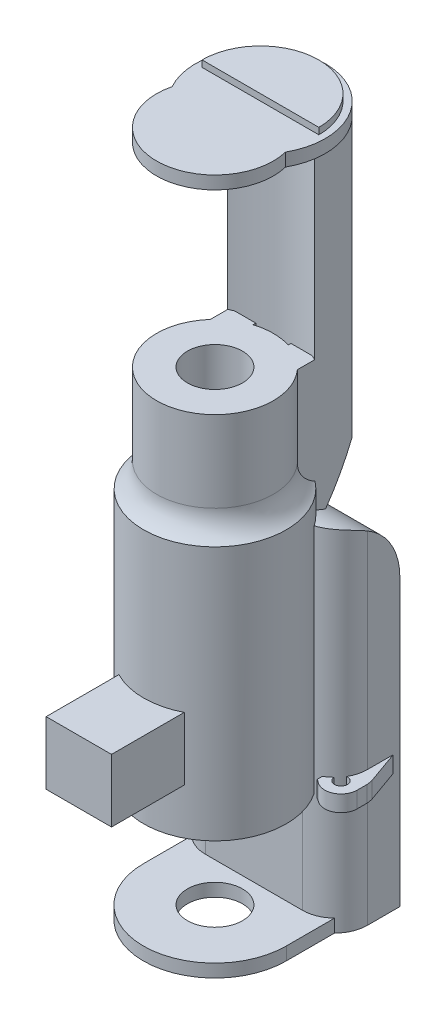
SolidWorks part; units mm, degrees
ref_plane "Front Plane" through (0, 0, 0) normal (0, 0, 1) x (1, 0, 0)
ref_plane "Top Plane" through (0, 0, 0) normal (0, 1, 0) x (1, 0, 0)
ref_plane "Right Plane" through (0, 0, 0) normal (1, 0, 0) x (0, 0, -1)
sketch "Sketch2" plane through (0, 0, 0) normal (0, 1, 0) x (1, 0, 0)
  line L0 (0, 12.9902) -> (0.0006, -12.9918) construction
  arc A0 (-8.7412, -1.8669) -> (8.7412, -1.8669) centre (0, -4.0082) ccw
  arc A1 (-8.7412, -1.8669) -> (8.7412, -1.8669) centre (0, 3.002) cw
extrude "Boss-Extrude1" add sketch "Sketch2" along normal blind 2
sketch "Sketch3" plane through (0, 2, 0) normal (0, 1, 0) x (1, 0, 0)
  line L0 (-9.0057, 3.002) -> (9.0057, 3.002)
  arc A6 (7.6664, -1.7234) -> (-7.6664, -1.7234) centre (0, 3.002) ccw
  arc A7 (-7.6664, -1.7234) -> (7.6664, -1.7234) centre (0, -4.0082) ccw
  arc A8 (9.0057, 3.002) -> (-9.0057, 3.002) centre (0, 3.002) ccw
  dimension "D1" = 1
extrude "Boss-Extrude2" add sketch "Sketch3" along normal blind 1
sketch "Sketch6" plane through (0, 0, 0) normal (0, -1, 0) x (1, 0, 0)
  line L0 (0, -13.0078) -> (0, -7.8404) construction
  line L1 (-6.7103, -10.4241) -> (6.7103, -10.4241) construction
  line L2 (-6.7103, -10.4241) -> (-6.7103, -4.6619)
  line L4 (6.7103, -4.6619) -> (6.7103, -10.4241)
  arc A0 (-8.7412, 1.8669) -> (8.7412, 1.8669) centre (0, -3.002) ccw construction
  arc A1 (-6.7103, -10.4241) -> (6.7103, -10.4241) centre (0, -3.1488) ccw
  arc A2 (-6.7103, -4.6619) -> (6.7103, -4.6619) centre (0, 8.915) ccw
  point P10 (0, -7.8404)
  point P11 (0, -10.4241)
extrude "Boss-Extrude3" add sketch "Sketch6" along normal blind 33
sketch "Sketch38" plane through (0, 0, 0) normal (1, 0, 0) x (0, 0, -1)
  line L0 (4.6619, -33) -> (4.6619, -53)
  line L1 (4.6619, -33) -> (13.0462, -33)
  arc A0 (13.0462, -33) -> (4.6619, -53) centre (-25.4769, -28.6081) cw
extrude "Boss-Extrude4" add sketch "Sketch38" along normal blind 7 and the other way blind 7
sketch "Sketch43" plane through (0, -33, 0) normal (0, 1, 0) x (1, 0, 0)
  line L0 (-6.7103, 4.6619) -> (6.7103, 4.6619)
  arc A0 (-6.7103, 4.6619) -> (6.7103, 4.6619) centre (0, -8.915) cw
extrude "Cut-Extrude2" cut sketch "Sketch43" against normal blind 21
sketch "Sketch44" plane through (0, -33, 0) normal (0, 1, 0) x (1, 0, 0)
  line L0 (0, 13.0462) -> (7, 13.0462)
  line L1 (7, 13.0462) -> (7, 4.6619)
  line L2 (7, 4.6619) -> (6.7103, 4.6619)
  line L3 (6.7103, 4.6619) -> (6.7103, 10.4241)
  arc A0 (6.7103, 10.4241) -> (0, 13.0462) centre (0, 3.1488) ccw
extrude "Cut-Extrude3" cut sketch "Sketch44" against normal blind 21
sketch "Sketch45" plane through (0, -33, 0) normal (0, 1, 0) x (1, 0, 0)
  line L0 (-6.7103, 4.6619) -> (-7, 4.6619)
  line L1 (-7, 4.6619) -> (-7, 13.0462)
  line L2 (-7, 13.0462) -> (0, 13.0462)
  line L3 (-6.7103, 10.4241) -> (-6.7103, 4.6619)
  arc A0 (6.7103, 10.4241) -> (-6.7103, 10.4241) centre (0, 3.1488) ccw construction
  arc A1 (0, 13.0462) -> (-6.7103, 10.4241) centre (0, 3.1488) ccw
extrude "Cut-Extrude4" cut sketch "Sketch45" against normal blind 21
sketch "Sketch46" plane through (0, 0, 0) normal (0, -1, 0) x (1, 0, 0)
  line L0 (-8.9996, 4.0082) -> (8.9996, 4.0082) construction
  circle A0 centre (0, 4.0082) radius 4.25
  arc A1 (8.7412, 1.8669) -> (-8.7412, 1.8669) centre (0, 4.0082) ccw construction
extrude "Cut-Extrude5" cut sketch "Sketch46" against normal blind 1
ref_plane "Plane1" through (0, -30, 0) normal (0, 1, 0) x (1, 0, 0)
sketch "Sketch47" plane through (0, -30, 0) normal (0, 1, 0) x (1, 0, 0)
  line L0 (-8.9996, -4.0082) -> (8.9996, -4.0082) construction
  arc A0 (-8.7412, -1.8669) -> (8.7412, -1.8669) centre (0, -4.0082) ccw construction
  circle A1 centre (0, -4.0082) radius 9
extrude "Boss-Extrude5" add sketch "Sketch47" against normal blind 17 separate body
ref_plane "Plane2" through (0, -47, 0) normal (0, 1, 0) x (1, 0, 0)
sketch "Sketch50" plane through (0, -47, 0) normal (0, 1, 0) x (1, 0, 0)
  line L0 (-8.9996, -4.0082) -> (8.9996, -4.0082) construction
  arc A0 (-8.7412, -1.8669) -> (8.7412, -1.8669) centre (0, -4.0082) ccw construction
  circle A1 centre (0, -4.0082) radius 11
extrude "Boss-Extrude6" add sketch "Sketch50" against normal blind 38.5
fillet "Fillet7" radius 4.5 1 edges at (0, -47, 13.0082)
ref_plane "Plane3" through (0, 0, -5) normal (0, 0, 1) x (1, 0, 0)
sketch "Sketch52" plane through (0, 0, -5) normal (0, 0, 1) x (1, 0, 0)
  line L0 (12.1, -30) -> (-12.1, -30) construction
  line L1 (-6.7103, -30) -> (-2.7103, -30)
  line L2 (-6.7103, -30) -> (-6.7103, -47)
  line L3 (-6.7103, -47) -> (-2.7103, -47)
  line L4 (-2.7103, -30) -> (-2.7103, -47)
  line L5 (-6.7103, -30) -> (-2.7103, -47) construction
  line L6 (-6.7103, -47) -> (-2.7103, -30) construction
  line L7 (-6.7103, -46.217) -> (-6.7103, 0) construction
  line L8 (12.1, -47) -> (-12.1, -47) construction
  line L9 (6.7103, -46.217) -> (6.7103, 0) construction
  line L10 (6.7103, -30) -> (2.7103, -30)
  line L11 (6.7103, -30) -> (6.7103, -47)
  line L12 (6.7103, -47) -> (2.7103, -47)
  line L13 (2.7103, -30) -> (2.7103, -47)
  line L14 (6.7103, -30) -> (2.7103, -47) construction
  line L15 (6.7103, -47) -> (2.7103, -30) construction
  point P4 (-4.7103, -38.5)
  point P15 (4.7103, -38.5)
  dimension "D1" = 4
  dimension "D2" = 4
extrude "Boss-Extrude7" add sketch "Sketch52" along normal blind 4.5
sketch "Sketch54" plane through (0, 0, -5) normal (0, 0, 1) x (1, 0, 0)
  line L0 (12.5, -49.8) -> (-12.5, -49.8) construction
  line L2 (12.5, -49.8) -> (-12.5, -49.8)
  line L3 (12.5, -49.8) -> (12.5, -103.8)
  line L4 (12.5, -103.8) -> (-12.5, -103.8)
  line L5 (-12.5, -49.8) -> (-12.5, -103.8)
  line L6 (12.5, -49.8) -> (-12.5, -103.8) construction
  line L7 (12.5, -103.8) -> (-12.5, -49.8) construction
  spline S1 degree 3 poles (-6.7103, -52.9429) (-6.2868, -52.5385) (-5.8353, -52.1509) (-5.1057, -51.6065) (-4.8537, -51.4313) (-4.3291, -51.0967) (-4.055, -50.9365) (-3.2088, -50.4935) (-2.6136, -50.2468) (-1.6563, -49.9838) (-1.3295, -49.9155) (-0.6727, -49.824) (-0.3409, -49.8002) (0.3301, -49.7997) (0.6674, -49.8235) (1.325, -49.9147) (1.6482, -49.982) (2.2847, -50.156) (2.5976, -50.2629) (3.1971, -50.5041) (3.4863, -50.6389) (4.3269, -51.0783) (4.8551, -51.4198) (5.8337, -52.1494) (6.2865, -52.5382) (6.7103, -52.9429) knots 0 0 0 0 0.125 0.125 0.1875 0.1875 0.25 0.25 0.375 0.375 0.4375 0.4375 0.5 0.5 0.5625 0.5625 0.625 0.625 0.6875 0.6875 0.75 0.75 0.875 0.875 1 1 1 1 construction
  point P3 (0, -49.8)
  point P7 (0, -76.8)
  dimension "D1" = 54
extrude "Boss-Extrude8" add sketch "Sketch54" against normal blind 7 and the other way blind 3
fillet "Fillet11" radius 10 1 edges at (0, -49.8, -12)
fillet "Fillet16" radius 5 2 edges at (12.5, -76.8, -2) (-12.5, -76.8, -2)
sketch "Sketch55" plane through (0, -103.8, 0) normal (0, -1, 0) x (1, 0, 0)
  line L0 (-11, -5) -> (11, -5)
  line L4 (-11, 4.0082) -> (-11, -5)
  line L5 (13.75, -5) -> (-13.75, -5) construction
  line L6 (11, 4.0082) -> (11, -5)
  arc A0 (-11, 4.0082) -> (11, 4.0082) centre (0, 4.0335) cw
  arc A1 (9.0491, -2.246) -> (-9.0491, -2.246) centre (0, 4.0082) ccw construction
extrude "Boss-Extrude9" add sketch "Sketch55" against normal blind 2
sketch "Sketch56" plane through (0, -30, 0) normal (0, 1, 0) x (1, 0, 0)
  line L0 (-9, -4.0082) -> (9, -4.0082) construction
  arc A0 (-6.7103, 1.9895) -> (6.7103, 1.9895) centre (0, -4.0082) ccw construction
  arc A1 (-6.7103, 1.9895) -> (6.7103, 1.9895) centre (0, -4.0082) ccw construction
  circle A2 centre (0, -4.0082) radius 4.25
extrude "Cut-Extrude6" cut sketch "Sketch56" against normal blind 83
ref_plane "Plane4" through (0, -85.5, 0) normal (0, 1, 0) x (1, 0, 0)
sketch "Sketch58" plane through (0, -85.5, 0) normal (0, 1, 0) x (1, 0, 0)
  line L0 (-12.5038, 10.9676) -> (-14.2844, 5.9548)
  line L1 (-14.4574, 4.9506) -> (-14.4574, 3.4675)
  line L2 (-9.935, 1.8145) -> (-9.935, 2.633)
  line L3 (-9.935, 2.633) -> (-11.0584, 3.4724)
  line L4 (-11.0584, 3.4724) -> (-11.5033, 4.0043)
  line L5 (-11.5033, 4.0043) -> (-11.7583, 4.3796)
  line L6 (-11.7583, 4.3796) -> (-11.8857, 4.6267)
  line L7 (-11.8857, 4.6267) -> (-12.1416, 5.1232)
  line L8 (-12.1416, 5.1232) -> (-12.2291, 5.3726)
  line L9 (-12.2291, 5.3726) -> (-12.2975, 5.567)
  line L10 (-12.2975, 5.567) -> (-12.4084, 6.0925)
  line L11 (-12.4084, 6.0925) -> (-12.4393, 6.239)
  line L12 (-12.4393, 6.239) -> (-12.5038, 6.9676)
  line L13 (-12.5038, 6.9676) -> (-12.5038, 8.8993)
  line L14 (-12.5038, 8.8993) -> (-12.5038, 9.6163)
  line L15 (-12.5038, 9.6163) -> (-12.5038, 10.7055)
  line L18 (0, -15.4438) -> (0, 15.4438) construction
  line L19 (12.5038, 10.9676) -> (14.2844, 5.9548)
  line L22 (12.5038, 9.6163) -> (12.5038, 10.7055)
  line L23 (12.5038, 8.8993) -> (12.5038, 9.6163)
  line L24 (12.5038, 6.9676) -> (12.5038, 8.8993)
  line L25 (12.4393, 6.239) -> (12.5038, 6.9676)
  line L26 (12.4084, 6.0925) -> (12.4393, 6.239)
  line L27 (12.2975, 5.567) -> (12.4084, 6.0925)
  line L28 (12.2291, 5.3726) -> (12.2975, 5.567)
  line L29 (12.1416, 5.1232) -> (12.2291, 5.3726)
  line L30 (11.8857, 4.6267) -> (12.1416, 5.1232)
  line L31 (11.7583, 4.3796) -> (11.8857, 4.6267)
  line L32 (11.5033, 4.0043) -> (11.7583, 4.3796)
  line L33 (11.0584, 3.4724) -> (11.5033, 4.0043)
  line L34 (9.935, 2.633) -> (11.0584, 3.4724)
  line L35 (9.935, 1.8145) -> (9.935, 2.633)
  line L36 (14.4574, 4.9506) -> (14.4574, 3.4675)
  line L37 (-12.5038, 10.9676) -> (-12.5038, 10.7055)
  line L38 (12.5038, 10.9676) -> (12.5038, 10.7055)
  arc A0 (-14.2844, 5.9548) -> (-14.4574, 4.9506) centre (-10.0366, 4.7058) ccw
  arc A1 (-14.4574, 3.4675) -> (-10.404, 1.509) centre (-11.9575, 3.4675) ccw
  arc A2 (-10.404, 1.509) -> (-9.935, 1.8145) centre (-8.5343, -0.8481) cw
  circle A3 centre (-11.9575, 3.4675) radius 1
  circle A4 centre (11.9575, 3.4675) radius 1
  arc A5 (10.404, 1.509) -> (9.935, 1.8145) centre (8.5343, -0.8481) ccw
  arc A6 (14.4574, 3.4675) -> (10.404, 1.509) centre (11.9575, 3.4675) cw
  arc A7 (14.2844, 5.9548) -> (14.4574, 4.9506) centre (10.0366, 4.7058) cw
  arc A8 (-12.5, 7) -> (-9.0491, 2.246) centre (-7.5, 7) ccw construction
  arc A9 (8.7412, -1.8669) -> (-8.7412, -1.8669) centre (0, 3.002) ccw construction
  arc A10 (-11, 3.4293) -> (-7.5, 2) centre (-7.5, 7) ccw construction
extrude "Boss-Extrude10" add sketch "Sketch58" along normal blind 2.5 contours A3 L6 L7 L8 L9 L10 L11 L12 L13 L14 L15 L37 L0 A0 L1 A1 A2 L2 L3 | A7 L19 L38 L22 L23 L24 L25 L26 L27 L28 L29 L30 L31 A4 L34 L35 A5 A6 L36 region at (-12.7906, -85.5, -4.4102) region at (12.7906, -85.5, -4.4102)
sketch "Sketch59" plane through (0, 0, -12) normal (0, 0, -1) x (-1, 0, 0)
  line L1 (-7.5, -79.9283) -> (7.5, -79.9283)
  line L2 (-7.5, -79.9283) -> (-7.5, -64.9283)
  line L3 (-7.5, -64.9283) -> (7.5, -64.9283)
  line L4 (7.5, -79.9283) -> (7.5, -64.9283)
  line L5 (-7.5, -79.9283) -> (7.5, -64.9283) construction
  line L6 (-7.5, -64.9283) -> (7.5, -79.9283) construction
  point P0 (0, -72.4283)
  dimension "D1" = 15
  dimension "D2" = 15
extrude "Cut-Extrude7" cut sketch "Sketch59" against normal blind 2.5
ref_plane "Plane6" through (0, 0, 15) normal (0, 0, 1) x (1, 0, 0)
sketch "Sketch61" plane through (0, 0, 15) normal (0, 0, 1) x (1, 0, 0)
  line L0 (-5.037, -68.7023) -> (5.0428, -68.7023)
  line L1 (-5.037, -68.7023) -> (-5.037, -78.4047)
  line L2 (-5.037, -78.4047) -> (5.0428, -78.4047)
  line L3 (5.0428, -68.7023) -> (5.0428, -78.4047)
  line L4 (-5.037, -68.7023) -> (5.0428, -78.4047) construction
  line L5 (-5.037, -78.4047) -> (5.0428, -68.7023) construction
  point P4 (0.0029, -73.5535)
extrude "Boss-Extrude11" add sketch "Sketch61" along normal blind 10 and the other way blind 10
